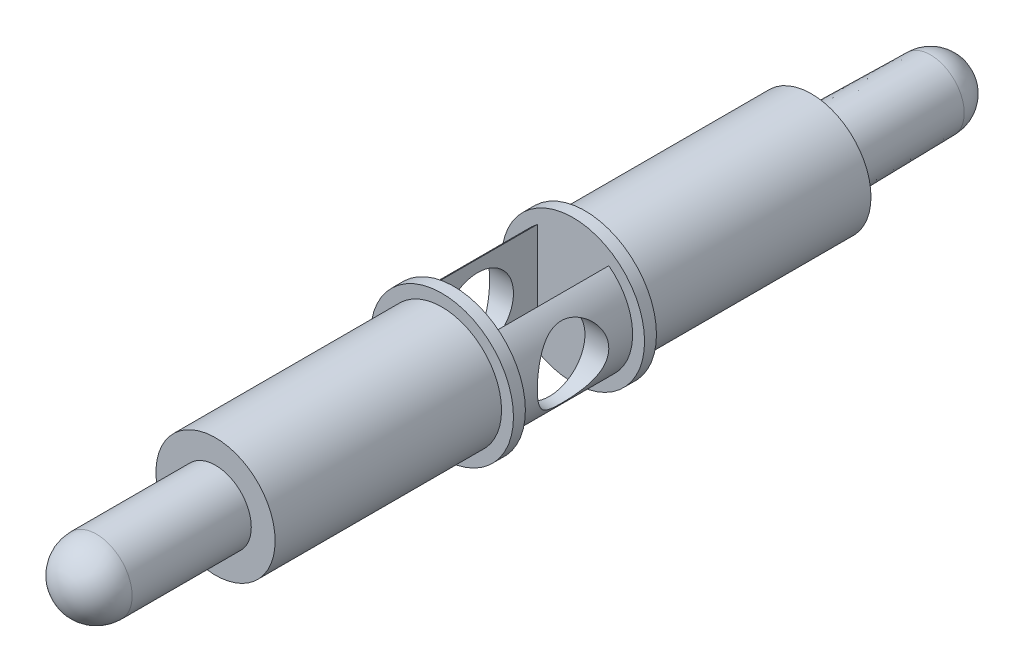
SolidWorks part; units mm, degrees
ref_plane "Front Plane" through (0, 0, 0) normal (0, 0, 1) x (1, 0, 0)
ref_plane "Top Plane" through (0, 0, 0) normal (0, 1, 0) x (1, 0, 0)
ref_plane "Right Plane" through (0, 0, 0) normal (1, 0, 0) x (0, 0, -1)
sketch "Sketch2" plane through (0, 0, 0) normal (0, 0, 1) x (1, 0, 0)
  circle A0 centre (0, 0) radius 5
  dimension "D1" = 10
extrude "Boss-Extrude1" add sketch "Sketch2" along normal blind 50
sketch "Sketch3" plane through (0, 0, 0) normal (0, 0, -1) x (-1, 0, 0)
  circle A0 centre (0, 0) radius 3
  dimension "D1" = 6
extrude "Boss-Extrude2" add sketch "Sketch3" along normal blind 10 draft 1
sketch "Sketch4" plane through (0, 0, -10) normal (0, 0, -1) x (-1, 0, 0)
  line L0 (0, 2.8254) -> (0, -2.8254)
  circle A0 centre (0, 0) radius 2.8254 construction
  arc A1 (0, -2.8254) -> (0, 2.8254) centre (0, 0) cw
sketch "Sketch5" plane through (0, 0, 50) normal (0, 0, 1) x (1, 0, 0)
  circle A0 centre (0, 0) radius 3
  dimension "D1" = 6
extrude "Boss-Extrude3" add sketch "Sketch5" along normal blind 10
sketch "Sketch6" plane through (0, 0, 60) normal (0, 0, 1) x (1, 0, 0)
  line L0 (0, 3) -> (0, -3)
  circle A0 centre (0, 0) radius 3 construction
  arc A1 (0, -3) -> (0, 3) centre (0, 0) cw
  dimension "D1" = 3
sketch "Sketch7" plane through (0, 0, 0) normal (0, 1, 0) x (1, 0, 0)
  line L0 (-5, 0) -> (5, -50) construction
  line L1 (-5, -50) -> (5, 0) construction
  line L3 (-3, -20) -> (3, -20)
  line L4 (-3, -20) -> (-3, -30)
  line L5 (-3, -30) -> (3, -30)
  line L6 (3, -20) -> (3, -30)
  line L7 (-3, -20) -> (3, -30) construction
  line L8 (-3, -30) -> (3, -20) construction
  point P8 (0, -25)
  dimension "D1" = 10
  dimension "D2" = 6
extrude "Cut-Extrude1" cut sketch "Sketch7" against normal blind 10 and the other way blind 10
sketch "Sketch8" plane through (0, 0, 0) normal (1, 0, 0) x (0, 0, -1)
  line L0 (-50, 5) -> (0, -5) construction
  line L1 (-50, 5) -> (-50, -5) construction
  line L2 (0, -5) -> (-50, -5) construction
  line L3 (-50, -5) -> (0, 5) construction
  line L4 (0, -5) -> (0, 5) construction
  circle A0 centre (-25, 0) radius 3
  dimension "D1" = 6
extrude "Cut-Extrude2" cut sketch "Sketch8" against normal blind 10 and the other way blind 10
revolve "Revolve1" add sketch "Sketch6" angle 360 about L0
revolve "Revolve2" add sketch "Sketch4" angle 360 about L0
ref_plane "Plane3" through (0, 0, 20) normal (0, 0, 1) x (1, 0, 0)
ref_plane "Plane4" through (0, 0, 30) normal (0, 0, 1) x (1, 0, 0)
sketch "Sketch10" plane through (0, 0, 20) normal (0, 0, 1) x (1, 0, 0)
  circle A0 centre (0, 0) radius 6
extrude "Boss-Extrude4" add sketch "Sketch10" against normal blind 1 contours A0
sketch "Sketch11" plane through (0, 0, 30) normal (0, 0, 1) x (1, 0, 0)
  circle A0 centre (0, 0) radius 6
  dimension "D1" = 12
extrude "Boss-Extrude5" add sketch "Sketch11" along normal blind 1
